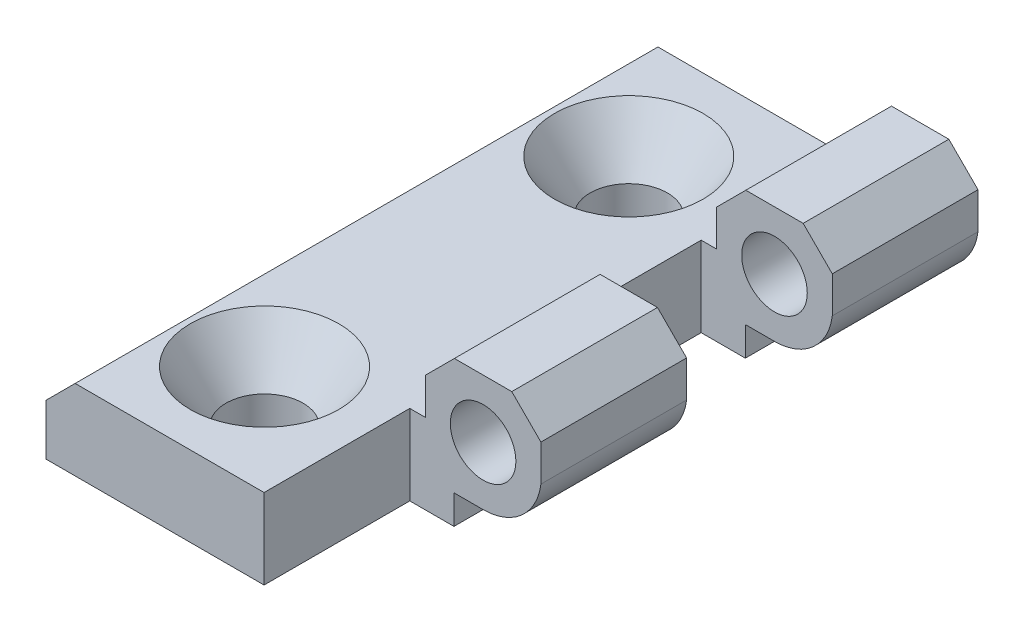
SolidWorks part; units mm, degrees
note: The reader was unsure of these and kept them because the rebuilt part matched: shared geometry of "草图3<2>".
ref_plane "前视基准面" through (0, 0, 0) normal (0, 0, 1) x (1, 0, 0)
ref_plane "上视基准面" through (0, 0, 0) normal (0, 1, 0) x (1, 0, 0)
ref_plane "右视基准面" through (0, 0, 0) normal (1, 0, 0) x (0, 0, -1)
sketch "草图1" plane through (0, 0, 0) normal (0, 1, 0) x (1, 0, 0)
  line L1 (-20, 20) -> (0, 20)
  line L2 (-20, 20) -> (-20, -20)
  line L3 (-20, -20) -> (0, -20)
  line L4 (0, 20) -> (0, -20)
  dimension "D1" = 40
  dimension "D2" = 20
extrude "凸台-拉伸1" add sketch "草图1" along normal blind 5.5
sketch "草图2" plane through (0, 0, 20) normal (0, 0, 1) x (1, 0, 0)
  line L1 (0, 0) -> (-2, 0)
  line L2 (0, 0) -> (0, 2)
  line L3 (0, 2) -> (-2, 2)
  line L4 (-2, 0) -> (-2, 2)
  dimension "D1" = 2
extrude "切除-拉伸1" cut sketch "草图2" against normal through all
sketch "草图3" plane through (0, 0, 20) normal (0, 0, 1) x (1, 0, 0)
  line L1 (-1.9686, 10) -> (1.9686, 10)
  line L2 (-3.9686, 5.5) -> (-3.9686, 8)
  line L3 (3.9686, 5.5) -> (3.9686, 8)
  line L4 (0, 6) -> (0, -6) construction
  line L5 (3.9686, 8) -> (1.9686, 10)
  line L6 (-3.9686, 8) -> (-1.9686, 10)
  line L8 (-20, 5.5) -> (0, 5.5) construction
  circle A0 centre (0, 6) radius 2.25
  arc A1 (-3.9686, 5.5) -> (3.9686, 5.5) centre (0, 6) ccw
  point P14 (0, 0)
  point P17 (0, 10)
  point P20 (0, 10)
  dimension "D5" = 4.5
  dimension "D1" = 6
  dimension "D2" = 45
  dimension "D3" = 4.5
  dimension "D4" = 2.5
extrude "凸台-拉伸2" add sketch "草图3" against normal up to surface (40 mm away) up to face at (-7.3333, 2.5, -20)
extrude "切除-拉伸2" cut sketch "草图3<2>" against normal through all contours A0
sketch "草图3<2>" plane through (0, 0, 20) normal (0, 0, 1) x (1, 0, 0) same geometry as "草图3"
chamfer "倒角1" distance 2 angle 45 1 edges at (-20, 5.5, 0)
sketch "草图4" plane through (0, 0, 0) normal (0, 1, 0) x (1, 0, 0)
  line L0 (3.9686, 20) -> (3.9686, -20) construction
  line L1 (-5.0314, 10) -> (3.9686, 10)
  line L2 (-5.0314, 10) -> (-5.0314, 0)
  line L3 (-5.0314, 0) -> (3.9686, 0)
  line L4 (3.9686, 10) -> (3.9686, 0)
  line L5 (-5.0314, -10) -> (3.9686, -10)
  line L6 (-5.0314, -10) -> (-5.0314, -20)
  line L7 (-5.0314, -20) -> (3.9686, -20)
  line L8 (3.9686, -10) -> (3.9686, -20)
  line L10 (-1.9686, 20) -> (1.9686, 20) construction
  dimension "D1" = 9
  dimension "D2" = 10
  dimension "D3" = 10
  dimension "D4" = 10
extrude "切除-拉伸3" cut sketch "草图4" along normal through all
hole_wizard "M5 十字切槽平头螺钉锥孔槽口3" positions "草图7" profile "草图8" size "M5" standard "IS" slot yes
sketch "草图7" plane through (0, 5.5, 0) normal (0, 1, 0) x (1, 0, 0)
  point P0 (-12.5, 12.5)
  point P2 (-12.5, -12.5)
  dimension "D1" = 25
  dimension "D2" = 12.5
  dimension "D3" = 12.5
sketch "草图8" plane through (-12.5, 5.5, -12.5) normal (1, 0, 0) x (0, 0, 1)
  line L0 (0, 0) -> (0, 7.5923)
  line L1 (0, 7.5923) -> (2.65, 6)
  line L2 (2.65, 6) -> (2.65, 3.499)
  line L3 (2.65, 3.499) -> (5.1, 0)
  line L5 (5.1, 0) -> (0, 0)
  line L6 (-2.65, 3.499) -> (-5.1, 0) construction
  line L10 (0, 7.5923) -> (-2.65, 6) construction
  line L11 (0, -6.35) -> (0, 107.95) construction
  dimension "孔直径" = 5.3
  dimension "孔深度" = 6
  dimension "近端锥形沉头孔直径" = 10.2
  dimension "近端锥形沉头孔角度" = 70
  dimension "导头角度" = 118
